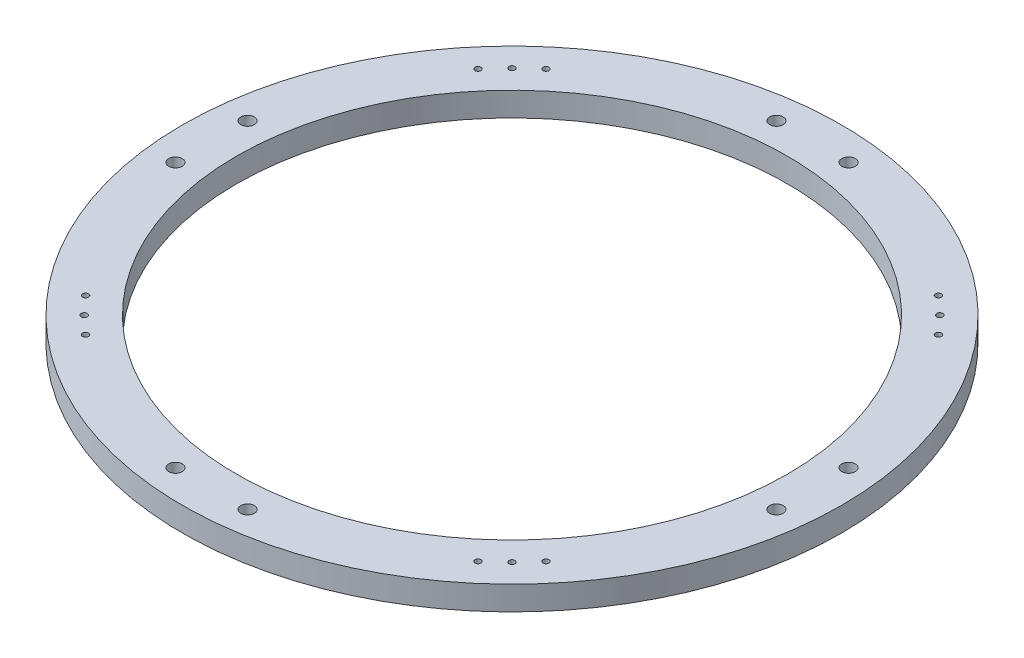
SolidWorks part; units mm, degrees
material "Oak"
ref_plane "Front Plane" through (0, 0, 0) normal (0, 0, 1) x (1, 0, 0)
ref_plane "Top Plane" through (0, 0, 0) normal (0, 1, 0) x (1, 0, 0)
ref_plane "Right Plane" through (0, 0, 0) normal (1, 0, 0) x (0, 0, -1)
sketch "Sketch1" plane through (0, 0, 0) normal (0, 0, 1) x (1, 0, 0)
  line L0 (0, -200000) -> (0, 218797.9879) construction
  line L5 (0, -200000) -> (0, 218797.9879) construction
  line L6 (174.1012, 209.4005) -> (174.1012, 196.7005)
  line L7 (145.5262, 209.4005) -> (174.1012, 209.4005)
  line L8 (174.1012, 196.7005) -> (145.5262, 196.7005)
  line L9 (145.5262, 196.7005) -> (145.5262, 209.4005)
revolve "Revolve1" add sketch "Sketch1" angle 360 about L5
hole_wizard "1/8 (0.125) Diameter Hole1" positions "Sketch5" profile "Sketch6" hole size "1/8" standard "ANSI Inch" end condition through all
sketch "Sketch5" plane through (0, 209.4005, 0) normal (0, 1, 0) x (1, 0, 0)
  point P0 (-113.0054, 113.0054)
  point P3 (-103.6677, 121.6282)
  point P6 (-121.6282, 103.6677)
sketch "Sketch6" plane through (-113.0054, 209.4005, -113.0054) normal (1, 0, 0) x (0, 0, 1)
  line L0 (0, 0) -> (0, 12.7)
  line L1 (0, 12.7) -> (1.5875, 12.7)
  line L2 (1.5875, 12.7) -> (1.5875, 0)
  line L5 (1.5875, 0) -> (0, 0)
  line L11 (0, -6.35) -> (0, 107.95) construction
  dimension "Thru Hole Dia." = 3.175
  dimension "Thru Hole Depth" = 12.7
sketch "Sketch7" plane through (0, 209.4005, 0) normal (0, 1, 0) x (1, 0, 0)
  line L0 (0, 0) -> (158.75, 0) construction
  line L1 (158.75, 19.05) -> (158.75, -19.05) construction
  circle A0 centre (158.75, -19.05) radius 3.5719
  circle A1 centre (158.75, 19.05) radius 3.5719
  point P6 (158.75, 0)
  dimension "D3" = 7.1437
  dimension "D1" = 38.1
  dimension "D2" = 158.75
extrude "Cut-Extrude1" cut sketch "Sketch7" against normal through all
pattern_circular "CirPattern1" count 4 over 360 about axis through (0, -200000, 0) along (0, -1, 0) of "1/8 (0.125) Diameter Hole1", "Cut-Extrude1"
